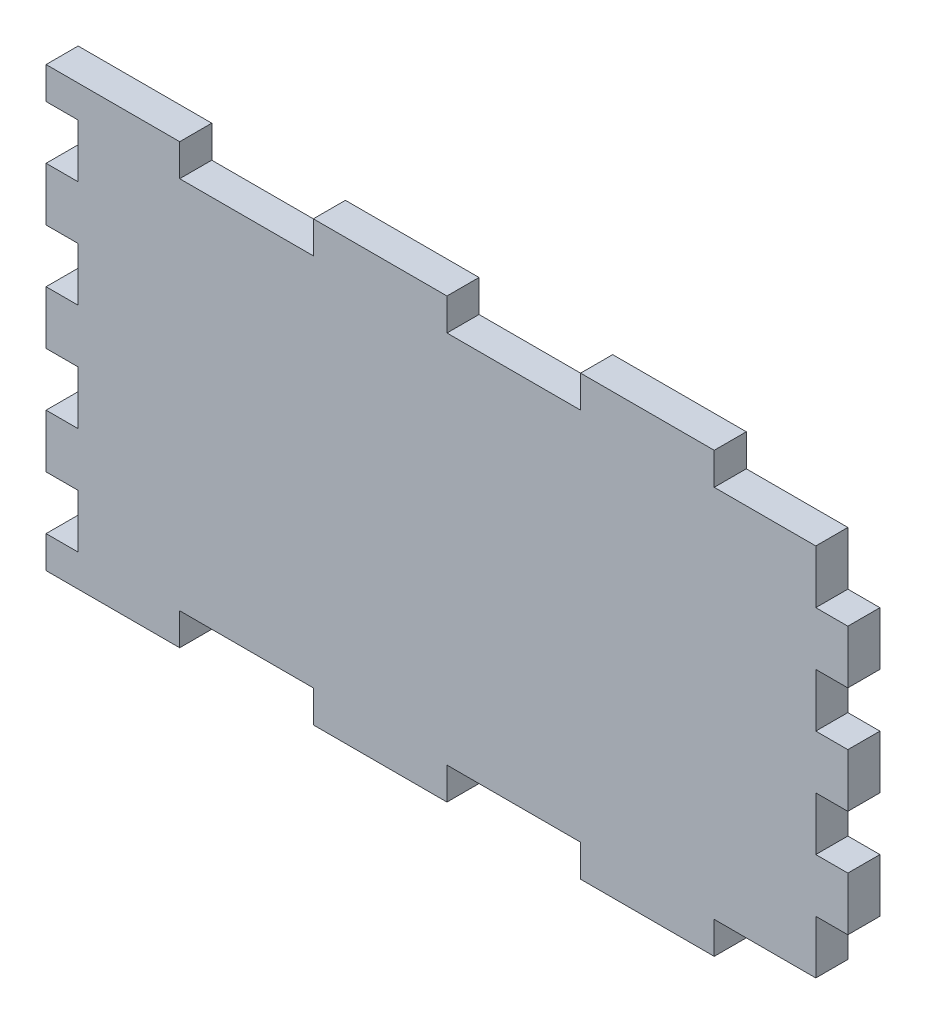
SolidWorks part; units mm, degrees
material "Pine"
ref_plane "Front Plane" through (0, 0, 0) normal (0, 0, 1) x (1, 0, 0)
ref_plane "Top Plane" through (0, 0, 0) normal (0, 1, 0) x (1, 0, 0)
ref_plane "Right Plane" through (0, 0, 0) normal (1, 0, 0) x (0, 0, -1)
sketch "Sketch1" plane through (0, 0, 0) normal (0, 0, 1) x (1, 0, 0)
  line L1 (-75, 41) -> (75, 41)
  line L2 (-75, 41) -> (-75, -41)
  line L3 (-75, -41) -> (75, -41)
  line L4 (75, 41) -> (75, -41)
  line L5 (-75, 41) -> (75, -41) construction
  line L6 (-75, -41) -> (75, 41) construction
  point P0 (0, 0)
  dimension "D1" = 150
  dimension "D2" = 82
extrude "Boss-Extrude1" add sketch "Sketch1" along normal blind 6
sketch "Sketch3" plane through (0, 0, 6) normal (0, 0, 1) x (1, 0, 0)
  line L0 (-75, 41) -> (-75, -41) construction
  line L1 (-75, 35) -> (-69, 35)
  line L2 (-75, 35) -> (-75, 25)
  line L3 (-75, 25) -> (-69, 25)
  line L4 (-69, 35) -> (-69, 25)
  line L5 (75, 41) -> (-75, 41) construction
  line L6 (69, 35) -> (69, 25)
  line L7 (69, 35) -> (75, 35)
  line L8 (75, 35) -> (75, 25)
  line L9 (69, 25) -> (75, 25)
  line L10 (69, 15) -> (69, 5)
  line L11 (69, 15) -> (75, 15)
  line L12 (75, 15) -> (75, 5)
  line L13 (69, 5) -> (75, 5)
  line L14 (-75, 15) -> (-75, 5)
  line L15 (-75, 15) -> (-69, 15)
  line L16 (-69, 15) -> (-69, 5)
  line L17 (-75, 5) -> (-69, 5)
  line L18 (-75, -5) -> (-75, -15)
  line L19 (-75, -5) -> (-69, -5)
  line L20 (-69, -5) -> (-69, -15)
  line L21 (-75, -15) -> (-69, -15)
  line L22 (69, -5) -> (69, -15)
  line L23 (69, -5) -> (75, -5)
  line L24 (75, -5) -> (75, -15)
  line L25 (69, -15) -> (75, -15)
  line L26 (-75, -25) -> (-75, -35)
  line L27 (-75, -25) -> (-69, -25)
  line L28 (-69, -25) -> (-69, -35)
  line L29 (-75, -35) -> (-69, -35)
  line L30 (69, -25) -> (69, -35)
  line L31 (69, -25) -> (75, -25)
  line L32 (75, -25) -> (75, -35)
  line L33 (69, -35) -> (75, -35)
  dimension "D1" = 6
  dimension "D2" = 10
  dimension "D3" = 6
  dimension "D4" = 2
  dimension "D5" = 4
extrude "Cut-Extrude1" cut sketch "Sketch3" against normal blind 10
sketch "Sketch4" plane through (0, 0, 6) normal (0, 0, 1) x (1, 0, 0)
  line L0 (25, -41) -> (25, -35)
  line L1 (75, -41) -> (50, -41)
  line L2 (75, -41) -> (75, -35)
  line L3 (75, -35) -> (50, -35)
  line L4 (50, -41) -> (50, -35)
  line L5 (25, -41) -> (0, -41)
  line L6 (0, -41) -> (0, -35)
  line L7 (25, -35) -> (0, -35)
  line L8 (-25, -41) -> (-25, -35)
  line L9 (-25, -41) -> (-50, -41)
  line L10 (-50, -41) -> (-50, -35)
  line L11 (-25, -35) -> (-50, -35)
  dimension "D1" = 25
  dimension "D2" = 6
  dimension "D3" = 3
extrude "Cut-Extrude2" cut sketch "Sketch4" against normal blind 6
mirror "Mirror1" about plane through (0, 0, 0) normal (0, 1, 0) of "Cut-Extrude2"
